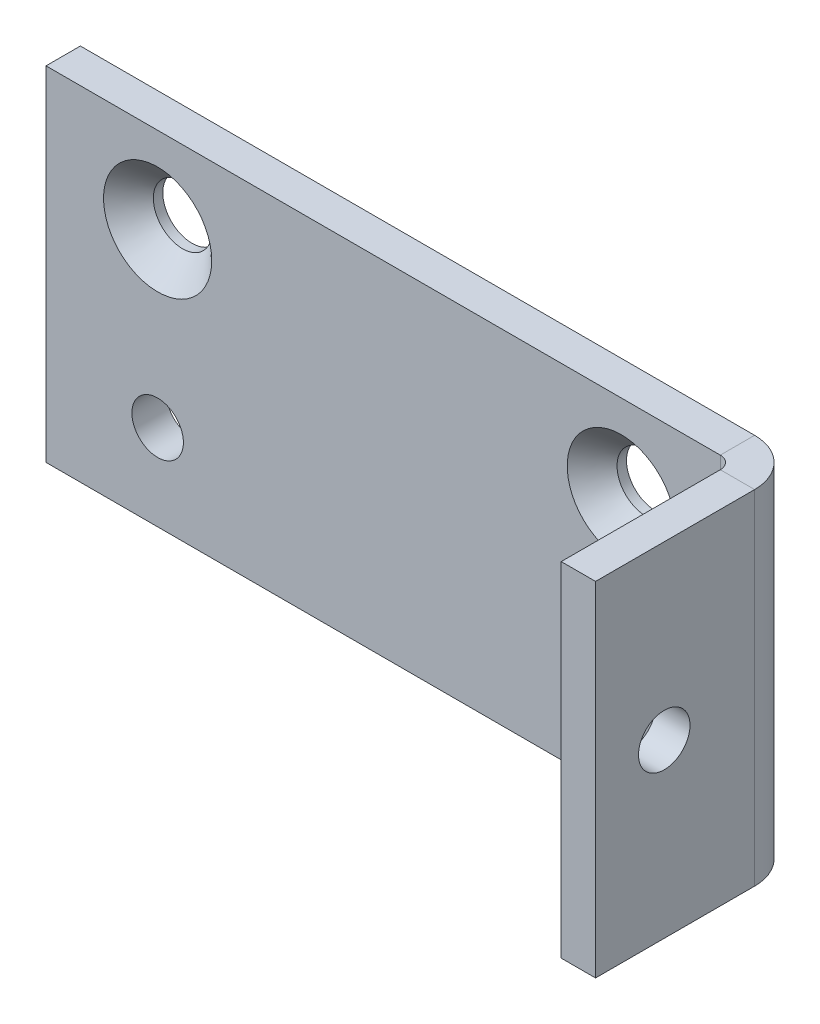
SolidWorks part; units mm, degrees
note: The reader was unsure of these and kept them because the rebuilt part matched: flange length of "邊線-凸緣1".
ref_plane "前基準面" through (0, 0, 0) normal (0, 0, 1) x (1, 0, 0)
ref_plane "上基準面" through (0, 0, 0) normal (0, 1, 0) x (1, 0, 0)
ref_plane "右基準面" through (0, 0, 0) normal (1, 0, 0) x (0, 0, -1)
sketch "草圖1" plane through (0, 0, 0) normal (0, 0, 1) x (1, 0, 0)
  line L0 (0, 10) -> (0, -10) construction
  line L1 (-20, 10) -> (20, 10)
  line L2 (-20, 10) -> (-20, -10)
  line L3 (-20, -10) -> (20, -10)
  line L4 (20, 10) -> (20, -10)
  dimension "D1" = 20
  dimension "D2" = 40
base flange "基材-凸緣1" sketch "草圖1" thickness 2 reverse thickness direction no parameters "D1"=0.7366
edge flange "邊線-凸緣1" sketch "草圖10" flange angle 90 flange length 12 flange position material outside bend radius 0.7366 thickness 2 relief rectangular parameters "D6"=10
sketch "草圖10" plane through (20, 0, 0) normal (1, 0, 0) x (0, 1, 0)
  line L0 (-10, 0) -> (10, 0) construction
  line L1 (-10, 0) -> (10, 0)
  line L2 (-10, 0) -> (-10, 10)
  line L3 (-10, 10) -> (10, 10)
  line L4 (10, 10) -> (10, 0)
bend "邊線彎折1" bend radius 0.7366 bend angle 90 parameters "D5"=1
hole_wizard "M3 平錐坑頭螺釘的錐孔2" positions "草圖12" profile "草圖11" countersink size "M3" standard "JIS" end condition through all
sketch "草圖12" plane through (0, 0, 0) normal (0, 0, 1) x (1, 0, 0)
  line L0 (19.2634, 10) -> (-20, 10) construction
  line L1 (-20, 10) -> (-20, -10) construction
  point P0 (-13.5, 5)
  point P3 (13.5, 5)
  dimension "D1" = 5
  dimension "D2" = 27
  dimension "D3" = 6.5
sketch "草圖11" plane through (-13.5, 5, 0) normal (1, 0, 0) x (0, -1, 0)
  line L0 (0, 0) -> (0, 2)
  line L1 (0, 2) -> (1.7, 2)
  line L2 (1.7, 2) -> (1.7, 1.45)
  line L3 (1.7, 1.45) -> (3.15, 0)
  line L5 (3.15, 0) -> (0, 0)
  line L6 (-1.7, 1.45) -> (-3.15, 0) construction
  line L11 (0, -6.35) -> (0, 107.95) construction
  dimension "貫穿孔直徑" = 3.4
  dimension "貫穿孔深度" = 2
  dimension "近端錐孔直徑" = 6.3
  dimension "近端錐孔角度" = 90
hole_wizard "M3 螺紋孔1" positions "草圖14" profile "草圖13" tap size "M3" standard "ISO" end condition through all
sketch "草圖14" plane through (22, 0, 0) normal (1, 0, 0) x (0, 0, -1)
  line L0 (0, 0) -> (-10, 0) construction
  line L1 (-10, 10) -> (-10, -10) construction
  line L3 (2, 10) -> (2, -10) construction
  point P0 (-6, 0)
  dimension "D1" = 8
sketch "草圖13" plane through (22, 0, 6) normal (0, 1, 0) x (0, 0, -1)
  line L0 (0, 0) -> (0, 42)
  line L1 (0, 42) -> (1.5, 42)
  line L2 (1.5, 42) -> (1.5, 0)
  line L5 (1.5, 0) -> (0, 0)
  line L11 (0, -6.35) -> (0, 107.95) construction
  dimension "貫穿螺孔鑽直徑" = 3
  dimension "貫穿螺孔鑽深度" = 42
hole_wizard "M3 螺紋孔2" positions "草圖16" profile "草圖15" tap size "M3" standard "ISO" end condition through all
sketch "草圖16" plane through (0, 0, -2) normal (0, 0, -1) x (-1, 0, 0)
  line L0 (20, -10) -> (-19.2634, -10) construction
  line L1 (20, 10) -> (20, -10) construction
  point P0 (-13.5, -5)
  point P3 (13.5, -5)
  dimension "D1" = 5
  dimension "D2" = 27
  dimension "D3" = 6.5
sketch "草圖15" plane through (13.5, -5, -2) normal (1, 0, 0) x (0, 1, 0)
  line L0 (0, 0) -> (0, 12)
  line L1 (0, 12) -> (1.5, 12)
  line L2 (1.5, 12) -> (1.5, 0)
  line L5 (1.5, 0) -> (0, 0)
  line L11 (0, -6.35) -> (0, 107.95) construction
  dimension "貫穿螺孔鑽直徑" = 3
  dimension "貫穿螺孔鑽深度" = 12
sketch "彎折-線1" plane through (0, 0, 0) normal (0, 1, 0) x (1, 0, 0)
sketch "邊界方塊1" plane through (0, 0, 0) normal (0, 1, 0) x (1, 0, 0)
sheet metal parameters "鈑金3" thickness 2 parameters "D1"=0.7366
flat pattern "平板-型式3" [suppressed]
sketch "彎折-線2" plane through (0, 0, 0) normal (0, 1, 0) x (1, 0, 0)
sketch "邊界方塊2" [suppressed] plane through (0, 0, 0) normal (0, 1, 0) x (1, 0, 0)
sheet metal parameters "鈑金4" thickness 2 parameters "D1"=0.7366
flat pattern "平板-型式3" [suppressed]
sketch "彎折-線2" plane through (0, 0, 0) normal (0, 1, 0) x (1, 0, 0)
sketch "邊界方塊2" [suppressed] plane through (0, 0, 0) normal (0, 1, 0) x (1, 0, 0)
bend of the flat pattern "平板-<邊線彎折1>1"
sheet metal parameters "鈑金5" thickness 2 parameters "D1"=0.7366
flat pattern "平板-型式3" [suppressed]
sketch "彎折-線2" plane through (0, 0, 0) normal (0, 1, 0) x (1, 0, 0)
sketch "邊界方塊2" [suppressed] plane through (0, 0, 0) normal (0, 1, 0) x (1, 0, 0)
bend of the flat pattern "平板-<邊線彎折1>1"
sheet metal parameters "鈑金6" thickness 2 parameters "D1"=0.7366
flat pattern "平板-型式3" [suppressed]
sketch "彎折-線2" plane through (0, 0, 0) normal (0, 1, 0) x (1, 0, 0)
sketch "邊界方塊2" [suppressed] plane through (0, 0, 0) normal (0, 1, 0) x (1, 0, 0)
bend of the flat pattern "平板-<邊線彎折1>1"
sheet metal parameters "鈑金7" thickness 2 parameters "D1"=0.7366
flat pattern "平板-型式3" [suppressed]
sketch "彎折-線2" plane through (0, 0, 0) normal (0, 1, 0) x (1, 0, 0)
sketch "邊界方塊2" [suppressed] plane through (0, 0, 0) normal (0, 1, 0) x (1, 0, 0)
bend of the flat pattern "平板-<邊線彎折1>1"
